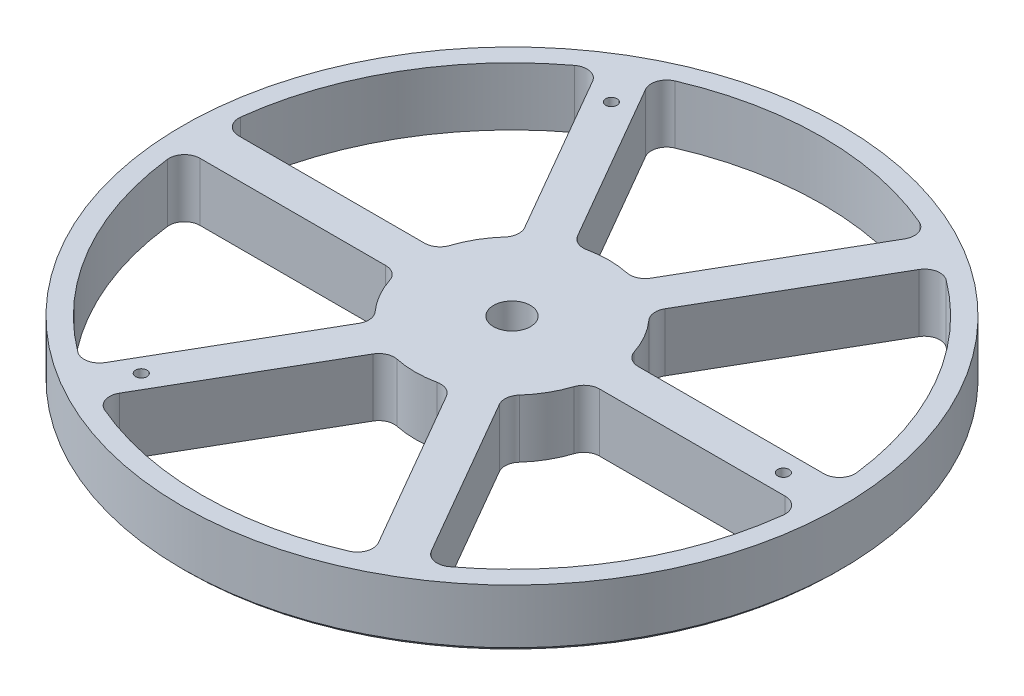
SolidWorks part; units mm, degrees
ref_plane "Front Plane" through (0, 0, 0) normal (0, 0, 1) x (1, 0, 0)
ref_plane "Top Plane" through (0, 0, 0) normal (0, 1, 0) x (1, 0, 0)
ref_plane "Right Plane" through (0, 0, 0) normal (1, 0, 0) x (0, 0, -1)
sketch "Sketch2" plane through (0, 0, 0) normal (1, 0, 0) x (0, 0, -1)
  line L0 (0, 0) -> (-84.9998, 0)
  line L1 (-84.9998, 0) -> (-84.9998, 15)
  line L2 (-84.9998, 15) -> (0, 15)
  line L5 (0, 15) -> (0, 0)
  point P3 (0, 0)
  point P6 (0, 0)
  point P8 (0, 0)
  dimension "D1" = 84.9998
  dimension "D2" = 15
ref_axis "Axis1" through (0, -0.75, 0) along (0, 1, 0)
revolve "Revolve1" add sketch "Sketch2" angle 360 about axis through (0, -0.75, 0) along (0, 1, 0)
hole_wizard "#32 (0.116) Diameter Hole1" positions "Sketch6" profile "Sketch7" hole size "#32" standard "ANSI Inch" end condition through all
sketch "Sketch6" plane through (0, 15, 0) normal (0, 1, 0) x (1, 0, 0)
  line L0 (0, 0) -> (-69.8201, 120.932) construction
  line L2 (0, 0) -> (0, 109.0908) construction
  point P0 (-35, 60.6218)
  dimension "D1" = 30
  dimension "D2" = 70
sketch "Sketch7" plane through (-35, 15, -60.6218) normal (1, 0, 0) x (0, 0, 1)
  line L0 (0, 0) -> (0, 15)
  line L1 (0, 15) -> (1.4732, 15)
  line L2 (1.4732, 15) -> (1.4732, 0)
  line L5 (1.4732, 0) -> (0, 0)
  line L11 (0, -6.35) -> (0, 107.95) construction
  dimension "Thru Hole Dia." = 2.9464
  dimension "Thru Hole Depth" = 15
pattern_circular "CirPattern3" count 3 over 360 about axis through (0, -0.75, 0) along (0, 1, 0) of "#32 (0.116) Diameter Hole1"
sketch "Sketch8" plane through (0, 15, 0) normal (0, 1, 0) x (1, 0, 0)
  line L4 (0, 0) -> (0, 93.9995) construction
  line L5 (0, 0) -> (113.8372, 0) construction
  line L6 (-7.9173, 23.7132) -> (-35.5916, 71.6464)
  line L7 (7.9173, 23.7132) -> (35.5916, 71.6464)
  line L8 (0, 0) -> (-35, 60.6218) construction
  arc A0 (-7.9173, 23.7132) -> (7.9173, 23.7132) centre (0, 0) cw
  arc A1 (-35.5916, 71.6464) -> (35.5916, 71.6464) centre (0, 0) cw
  circle A2 centre (0, 0) radius 84.9998 construction
  point P4 (0, 0)
  point P9 (0, 0)
  dimension "D1" = 25
  dimension "D2" = 5
  dimension "D3" = 5
extrude "Cut-Extrude1" cut sketch "Sketch8" against normal through all
fillet "Fillet1" radius 4 4 edges at (7.9173, 7.5, -23.7132) (35.5916, 7.5, -71.6464) (-7.9173, 7.5, -23.7132) (-35.5916, 7.5, -71.6464)
pattern_circular "CirPattern4" count 6 over 360 about axis through (0, -0.75, 0) along (0, 1, 0) of "Cut-Extrude1", "Fillet1"
chamfer "Chamfer2" distance 1 angle 45 1 edges at (0, 0, -84.9998)
hole_wizard "3/8 (0.375) Diameter Hole1" positions "Sketch9" profile "Sketch11" hole size "3/8" standard "ANSI Inch" end condition through all
sketch "Sketch9" plane through (0, 0, 0) normal (0, -1, 0) x (-1, 0, 0)
  point P0 (0, 0)
sketch "Sketch11" plane through (0, 0, 0) normal (1, 0, 0) x (0, 0, -1)
  line L0 (0, 0) -> (0, 15)
  line L1 (0, 15) -> (4.7625, 15)
  line L2 (4.7625, 15) -> (4.7625, 0)
  line L5 (4.7625, 0) -> (0, 0)
  line L11 (0, -6.35) -> (0, 107.95) construction
  dimension "Thru Hole Dia." = 9.525
  dimension "Thru Hole Depth" = 15
